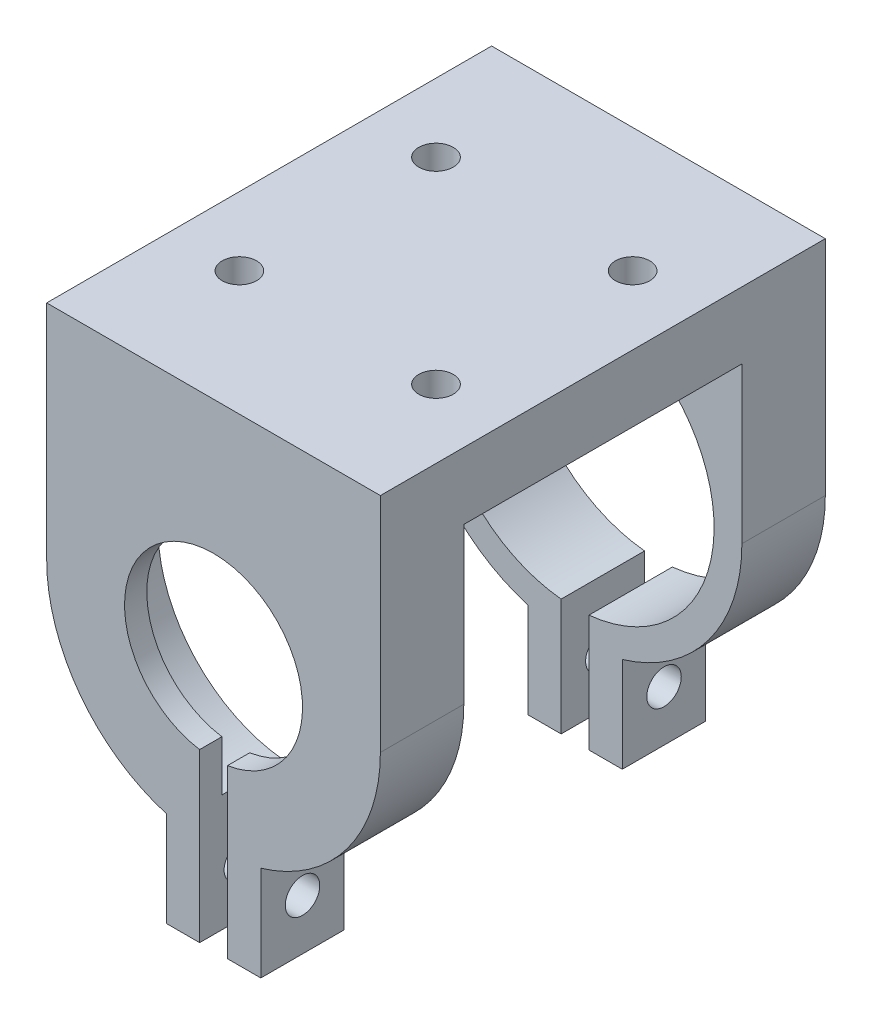
SolidWorks part; units mm, degrees
material "PLA"
ref_plane "Front Plane" through (0, 0, 0) normal (0, 0, 1) x (1, 0, 0)
ref_plane "Top Plane" through (0, 0, 0) normal (0, 1, 0) x (1, 0, 0)
ref_plane "Right Plane" through (0, 0, 0) normal (1, 0, 0) x (0, 0, -1)
sketch "Sketch1" plane through (0, 0, 0) normal (0, 0, 1) x (1, 0, 0)
  line L0 (-15, 0) -> (-15, 15)
  line L1 (-15, 15) -> (15, 15)
  line L2 (15, 15) -> (15, 0)
  line L4 (-1.25, -17.4373) -> (1.25, -17.4373)
  line L5 (-1.25, -17.4373) -> (-1.25, -12.4373)
  line L6 (-1.25, -12.4373) -> (1.25, -12.4373)
  line L7 (1.25, -17.4373) -> (1.25, -12.4373)
  line L8 (0, -44.7868) -> (0, 44.7868) construction
  circle A0 centre (0, 0) radius 12.5
  circle A1 centre (0, 0) radius 15
  dimension "D1" = 25
  dimension "D2" = 30
  dimension "D3" = 2.5
  dimension "D4" = 1.25
  dimension "D5" = 5
extrude "Boss-Extrude1" add sketch "Sketch1" along normal mid plane 40 contours A1 L1 L0 | A1 L2 L1 | A1 L5 A0 L7 region at (-11.6495, 11.6495, 0) region at (-10.3069, 10.3069, 0) region at (11.6495, 11.6495, 0)
sketch "Sketch2" plane through (0, 0, 0) normal (0, 0, 1) x (1, 0, 0)
  line L1 (-1.25, -12.4373) -> (-4.25, -12.4373)
  line L2 (-1.25, -12.4373) -> (-1.25, -22.9373)
  line L3 (-1.25, -22.9373) -> (-4.25, -22.9373)
  line L4 (-4.25, -12.4373) -> (-4.25, -22.9373)
  line L5 (1.25, -12.4373) -> (4.25, -12.4373)
  line L6 (1.25, -12.4373) -> (1.25, -22.9373)
  line L7 (1.25, -22.9373) -> (4.25, -22.9373)
  line L8 (4.25, -12.4373) -> (4.25, -22.9373)
  dimension "D1" = 3
  dimension "D2" = 10.5
extrude "Boss-Extrude2" add sketch "Sketch2" along normal mid plane 40
sketch "Sketch4" plane through (0, 15, 0) normal (0, 1, 0) x (1, 0, 0)
  line L0 (-15, -20) -> (-15, 20) construction
  line L1 (-15, 20) -> (15, 20)
  line L2 (-15, 20) -> (-15, -20)
  line L3 (-15, -20) -> (15, -20)
  line L4 (15, 20) -> (15, -20)
  line L5 (15, -20) -> (15, 20) construction
  line L6 (-44.2539, 0) -> (44.2539, 0) construction
  dimension "D1" = 40
  dimension "D2" = 20
extrude "Boss-Extrude3" add sketch "Sketch4" along normal blind 5
sketch "Sketch5" plane through (15, 0, 0) normal (1, 0, 0) x (0, 0, -1)
  line L0 (-20, -22.9373) -> (20, -22.9373) construction
  line L1 (-12.5, 14) -> (12.5, 14)
  line L2 (-12.5, 14) -> (-12.5, -22.9373)
  line L3 (-12.5, -22.9373) -> (12.5, -22.9373)
  line L4 (12.5, 14) -> (12.5, -22.9373)
  line L5 (0, 44.2539) -> (0, -44.2539) construction
  line L6 (-20, 20) -> (20, 20) construction
  dimension "D1" = 25
  dimension "D2" = 12.5
  dimension "D3" = 6
extrude "Cut-Extrude2" cut sketch "Sketch5" along direction (-1, 0, 0) on the side against the normal offset from surface (13 mm away) 2 up to plane "Right Plane"
sketch "Sketch6" plane through (0, 20, 0) normal (0, 1, 0) x (1, 0, 0)
  line L0 (-44.2539, 0) -> (44.2539, 0) construction
  line L1 (-8.8388, 8.8388) -> (8.8388, 8.8388) construction
  line L2 (-8.8388, 8.8388) -> (-8.8388, -8.8388) construction
  line L3 (-8.8388, -8.8388) -> (8.8388, -8.8388) construction
  line L4 (8.8388, 8.8388) -> (8.8388, -8.8388) construction
  line L5 (0, -44.7868) -> (0, 44.7868) construction
  circle A0 centre (-8.8388, 8.8388) radius 1.55
  circle A1 centre (8.8388, 8.8388) radius 1.55
  circle A2 centre (8.8388, -8.8388) radius 1.55
  circle A3 centre (-8.8388, -8.8388) radius 1.55
  point P6 (-8.8388, 0)
  point P7 (0, 8.8388)
  dimension "D1" = 25
  dimension "D2" = 3.1
extrude "MotorMountHoles" cut sketch "Sketch6" against normal up to surface (6 mm away) up to face at (8.5, 14, 0)
sketch "Sketch7" plane through (0, 14, 0) normal (0, -1, 0) x (1, 0, 0)
  circle A0 centre (8.8388, 8.8388) radius 2.55
  dimension "D1" = 5.1
extrude "M3ScrewHeadGuide" [suppressed] add sketch "Sketch7" along normal blind 3
sketch "Sketch8" plane through (-4.25, 0, 0) normal (-1, 0, 0) x (0, 0, 1)
  line L1 (20, -14.3853) -> (20, -22.9373) construction
  line L2 (20, -14.3853) -> (-20, -14.3853) construction
  line L3 (-12.5, -22.9373) -> (-12.5, -14.3853) construction
  line L4 (20, -14.3853) -> (-20, -14.3853) construction
  circle A0 centre (16.25, -18.3853) radius 1.55
  circle A1 centre (-16.25, -18.3853) radius 1.55
  dimension "D1" = 3.1
  dimension "D2" = 3.75
  dimension "D3" = 4
  dimension "D4" = 3.75
  dimension "D5" = 4
extrude "ClampHoles" cut sketch "Sketch8" against normal up to surface (8.5 mm away) up to face at (4.25, -18.6613, 16.25)
sketch "Sketch9" plane through (0, 0, 20) normal (0, 0, 1) x (1, 0, 0)
  line L1 (-1.25, -12.4373) -> (1.25, -12.4373)
  line L2 (-1.25, -12.4373) -> (-1.25, -7.9017)
  line L3 (-1.25, -7.9017) -> (1.25, -7.9017)
  line L4 (1.25, -12.4373) -> (1.25, -7.9017)
  circle A0 centre (0, 0) radius 12.5
  circle A1 centre (0, 0) radius 8
  point P9 (0, 0)
  point P11 (0, 0)
  point P12 (-1.25, -6.7378)
  arc M13 (-1.25, -12.4373) -> (1.25, -12.4373) centre (0, 0) cw
  dimension "D1" = 16
  dimension "D2" = 25
extrude "EndStopper" add sketch "Sketch9" against normal blind 2 contours A1 L4 L2 M13 region at (-8.1484, 9.0084, 20)
sketch "Sketch10" plane through (0, 0, 0) normal (1, 0, 0) x (0, 0, -1)
  line L1 (-12.5, 14) -> (12.5, 14)
  line L2 (-12.5, 14) -> (-12.5, -22.9373)
  line L3 (-12.5, -22.9373) -> (12.5, -22.9373)
  line L4 (12.5, 14) -> (12.5, -22.9373)
extrude "Cut-Extrude7" cut sketch "Sketch10" along normal offset from surface (13 mm away) 2 from surface up to plane "Right Plane" starting at face at (-15, 10, 0)
sketch "Sketch11" plane through (-2, 0, 0) normal (-1, 0, 0) x (0, 0, 1)
  line L1 (-12.5, -12.339) -> (12.5, -12.339)
  line L2 (-12.5, -12.339) -> (-12.5, -22.9373)
  line L3 (-12.5, -22.9373) -> (12.5, -22.9373)
  line L4 (12.5, -12.339) -> (12.5, -22.9373)
extrude "Cut-Extrude8" cut sketch "Sketch11" against normal up to surface (4 mm away) up to face at (2, -17.6382, 0)
equation "\"InnerDiam\"=25"
equation "\"D1@Sketch1\"=\"InnerDiam\""
equation "\"OuterDiam\"=30"
equation "\"D2@Sketch1\"=\"OuterDiam\""
equation "\"TightenGap\"= 2.5"
equation "\"D3@Sketch1\"=\"TightenGap\""
equation "\"D4@Sketch1\"=\"TightenGap\"/2"
equation "\"D5@Sketch1\"=\"OuterDiam\"-\"InnerDiam\""
equation "\"ClampLen\"=10.5"
equation "\"D2@Sketch2\"=\"ClampLen\""
equation "\"Thick\"=40"
equation "\"D1@Boss-Extrude2\"=\"Thick\""
equation "\"D1@Boss-Extrude1\"=\"Thick\""
equation "\"MotBaseThick\"=5"
equation "\"D1@Boss-Extrude3\"=\"MotBaseThick\""
equation "\"TopPlateLen\"=35"
equation "\"D1@Sketch4\"=\"Thick\""
equation "\"D2@Sketch4\"=\"Thick\"/2"
equation "\"D1@Sketch5\"=\"Thick\"- 2 * \"ClampWidth\""
equation "\"D2@Sketch5\"=(\"Thick\"- 2 * \"ClampWidth\")/2"
equation "\"MotorMountDiam\"=25"
equation "\"D1@Sketch6\"=\"MotorMountDiam\""
equation "\"ClampWidth\"= 7.5"
equation "\"D2@Sketch8\"=\"ClampWidth\"/2"
equation "\"D3@Sketch8\"=(\"ClampLen\"- 2.5)/2"
equation "\"D4@Sketch8\"=\"ClampWidth\"/2"
equation "\"D5@Sketch8\"=(\"ClampLen\"- 2.5)/2"
equation "\"D2@Sketch9\"=\"InnerDiam\""
equation "\"D19@Cut-Extrude2\"=\"OuterDiam\"/2"
